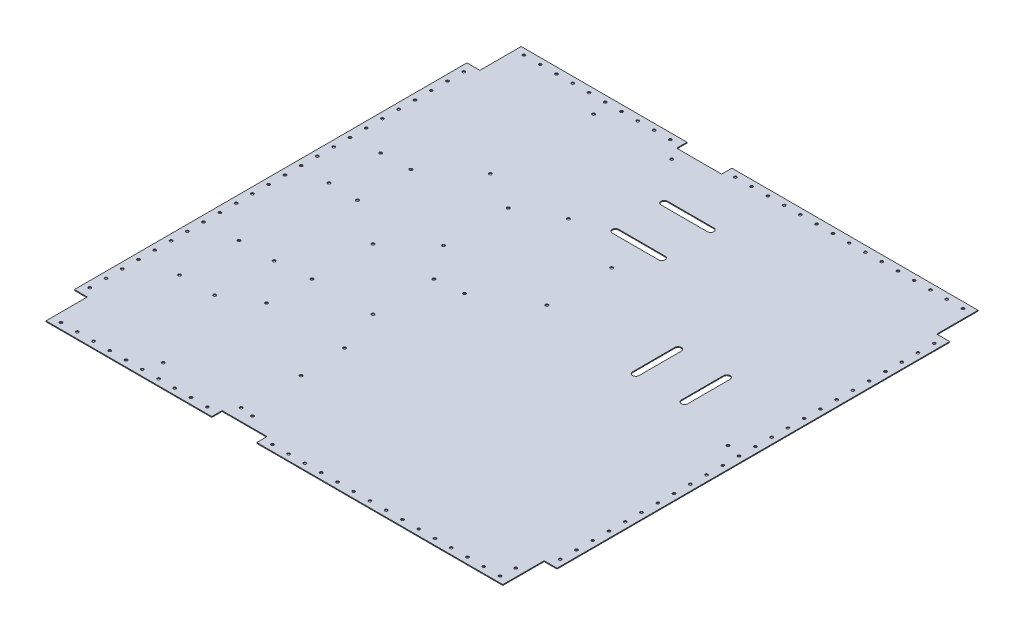
SolidWorks part; units mm, degrees
ref_plane "Front Plane" through (0, 0, 0) normal (0, 0, 1) x (1, 0, 0)
ref_plane "Top Plane" through (0, 0, 0) normal (0, 1, 0) x (1, 0, 0)
ref_plane "Right Plane" through (0, 0, 0) normal (1, 0, 0) x (0, 0, -1)
sketch "Sketch1" plane through (0, 0, 0) normal (0, 1, 0) x (1, 0, 0)
  line L1 (0, 0) -> (914.4, 0)
  line L2 (0, 0) -> (0, 609.6)
  line L3 (0, 609.6) -> (914.4, 609.6)
  line L4 (914.4, 0) -> (914.4, 609.6)
  dimension "D1" = 914.4
  dimension "D2" = 609.6
base flange "Base-Flange1" sketch "Sketch1" thickness 1.016 reverse thickness direction no parameters "D1"=0.7366
sketch "Sketch6" plane through (0, 0, 0) normal (0, 1, 0) x (1, 0, 0)
  line L0 (0, 0) -> (914.4, 0) construction
  line L1 (176.255, 597.025) -> (380.175, 597.025)
  line L2 (160.375, 546.225) -> (160.375, 63.375)
  line L3 (176.255, 12.575) -> (380.175, 12.575)
  line L4 (754.025, 546.225) -> (754.025, 63.375)
  line L5 (176.255, 581.3911) -> (738.145, 28.2089) construction
  line L6 (176.255, 28.2089) -> (738.145, 581.3911) construction
  line L7 (914.4, 0) -> (914.4, 609.6) construction
  line L8 (160.375, 304.8) -> (754.025, 304.8) construction
  line L10 (380.175, 597.025) -> (380.175, 584.325)
  line L11 (380.175, 584.325) -> (435.475, 584.325)
  line L12 (435.475, 597.025) -> (435.475, 584.325)
  line L15 (754.025, 546.225) -> (738.145, 546.225)
  line L16 (738.145, 597.025) -> (738.145, 546.225)
  line L17 (435.475, 12.575) -> (435.475, 25.275)
  line L18 (380.175, 12.575) -> (380.175, 25.275)
  line L19 (380.175, 25.275) -> (435.475, 25.275)
  line L20 (754.025, 63.375) -> (738.145, 63.375)
  line L21 (738.145, 12.575) -> (738.145, 63.375)
  line L22 (457.2, 597.025) -> (457.2, 12.575) construction
  line L23 (176.255, 12.575) -> (176.255, 63.375)
  line L24 (160.375, 63.375) -> (176.255, 63.375)
  line L25 (160.375, 546.225) -> (176.255, 546.225)
  line L26 (176.255, 597.025) -> (176.255, 546.225)
  line L27 (0, 609.6) -> (0, 0) construction
  line L28 (435.475, 597.025) -> (738.145, 597.025)
  line L29 (435.475, 12.575) -> (738.145, 12.575)
  point P0 (457.2, 304.8)
  dimension "D1" = 304.8
  dimension "D2" = 457.2
  dimension "D3" = 160.375
  dimension "D4" = 12.575
  dimension "D5" = 219.8
  dimension "D6" = 55.3
  dimension "D7" = 50.8
  dimension "D8" = 15.88
  dimension "D9" = 12.7
  dimension "D10" = 28.2089
extrude "Cut-Extrude1" cut sketch "Sketch6" against normal blind 10 flip side to cut normal cut yes
sketch "Sketch8" plane through (0, -1.016, 0) normal (0, -1, 0) x (1, 0, 0)
  line L0 (754.025, -546.225) -> (754.025, -63.375) construction
  line L1 (754.025, -63.375) -> (738.145, -63.375) construction
  line L20 (176.255, -597.025) -> (380.175, -597.025)
  line L21 (380.175, -597.025) -> (380.175, -584.325)
  line L22 (380.175, -584.325) -> (435.475, -584.325)
  line L23 (435.475, -584.325) -> (435.475, -597.025)
  line L24 (435.475, -597.025) -> (738.145, -597.025)
  line L25 (738.145, -597.025) -> (738.145, -546.225)
  line L26 (738.145, -546.225) -> (754.025, -546.225)
  line L27 (754.025, -546.225) -> (754.025, -63.375)
  line L28 (754.025, -63.375) -> (738.145, -63.375)
  line L29 (738.145, -63.375) -> (738.145, -12.575)
  line L30 (738.145, -12.575) -> (435.475, -12.575)
  line L31 (435.475, -12.575) -> (435.475, -25.275)
  line L32 (435.475, -25.275) -> (380.175, -25.275)
  line L33 (380.175, -25.275) -> (380.175, -12.575)
  line L34 (380.175, -12.575) -> (176.255, -12.575)
  line L35 (176.255, -12.575) -> (176.255, -63.375)
  line L36 (176.255, -63.375) -> (160.375, -63.375)
  line L37 (160.375, -63.375) -> (160.375, -546.225)
  line L38 (160.375, -546.225) -> (176.255, -546.225)
  line L39 (176.255, -546.225) -> (176.255, -597.025)
  line L40 (176.255, -597.025) -> (380.175, -597.025)
  line L41 (380.175, -597.025) -> (380.175, -584.325)
  line L42 (380.175, -584.325) -> (435.475, -584.325)
  line L43 (435.475, -584.325) -> (435.475, -597.025)
  line L44 (435.475, -597.025) -> (738.145, -597.025)
  line L45 (738.145, -597.025) -> (738.145, -546.225)
  line L46 (738.145, -546.225) -> (754.025, -546.225)
  line L47 (754.025, -546.225) -> (754.025, -63.375)
  line L48 (754.025, -63.375) -> (738.145, -63.375)
  line L49 (738.145, -63.375) -> (738.145, -12.575)
  line L50 (738.145, -12.575) -> (435.475, -12.575)
  line L51 (435.475, -12.575) -> (435.475, -25.275)
  line L52 (435.475, -25.275) -> (380.175, -25.275)
  line L53 (380.175, -25.275) -> (380.175, -12.575)
  line L54 (380.175, -12.575) -> (176.255, -12.575)
  line L55 (176.255, -12.575) -> (176.255, -63.375)
  line L56 (176.255, -63.375) -> (160.375, -63.375)
  line L57 (160.375, -63.375) -> (160.375, -546.225)
  line L58 (160.375, -546.225) -> (176.255, -546.225)
  line L59 (176.255, -546.225) -> (176.255, -597.025)
  circle A0 centre (167.875, -534.8) radius 1.675
  circle A1 centre (167.875, -514.8) radius 1.675
  circle A2 centre (167.875, -494.8) radius 1.675
  circle A3 centre (167.875, -474.8) radius 1.675
  circle A4 centre (167.875, -454.8) radius 1.675
  circle A5 centre (167.875, -434.8) radius 1.675
  circle A6 centre (167.875, -414.8) radius 1.675
  circle A7 centre (167.875, -394.8) radius 1.675
  circle A8 centre (167.875, -374.8) radius 1.675
  circle A9 centre (167.875, -354.8) radius 1.675
  circle A10 centre (167.875, -334.8) radius 1.675
  circle A11 centre (167.875, -314.8) radius 1.675
  circle A12 centre (167.875, -294.8) radius 1.675
  circle A13 centre (167.875, -274.8) radius 1.675
  circle A14 centre (167.875, -254.8) radius 1.675
  circle A15 centre (167.875, -234.8) radius 1.675
  circle A16 centre (167.875, -214.8) radius 1.675
  circle A17 centre (167.875, -194.8) radius 1.675
  circle A18 centre (167.875, -174.8) radius 1.675
  circle A19 centre (167.875, -154.8) radius 1.675
  circle A20 centre (167.875, -134.8) radius 1.675
  circle A21 centre (167.875, -114.8) radius 1.675
  circle A22 centre (167.875, -94.8) radius 1.675
  circle A23 centre (167.875, -74.8) radius 1.675
  circle A24 centre (187.2, -20.075) radius 1.675
  circle A25 centre (207.2, -20.075) radius 1.675
  circle A26 centre (227.2, -20.075) radius 1.675
  circle A27 centre (247.2, -20.075) radius 1.675
  circle A28 centre (267.2, -20.075) radius 1.675
  circle A29 centre (287.2, -20.075) radius 1.675
  circle A30 centre (307.2, -20.075) radius 1.675
  circle A31 centre (327.2, -20.075) radius 1.675
  circle A32 centre (347.2, -20.075) radius 1.675
  circle A33 centre (367.2, -20.075) radius 1.675
  circle A34 centre (447.2, -20.075) radius 1.675
  circle A35 centre (467.2, -20.075) radius 1.675
  circle A36 centre (487.2, -20.075) radius 1.675
  circle A37 centre (507.2, -20.075) radius 1.675
  circle A38 centre (527.2, -20.075) radius 1.675
  circle A39 centre (547.2, -20.075) radius 1.675
  circle A40 centre (567.2, -20.075) radius 1.675
  circle A41 centre (587.2, -20.075) radius 1.675
  circle A42 centre (607.2, -20.075) radius 1.675
  circle A43 centre (627.2, -20.075) radius 1.675
  circle A44 centre (647.2, -20.075) radius 1.675
  circle A45 centre (667.2, -20.075) radius 1.675
  circle A46 centre (687.2, -20.075) radius 1.675
  circle A47 centre (707.2, -20.075) radius 1.675
  circle A48 centre (727.2, -20.075) radius 1.675
  circle A49 centre (746.525, -74.8) radius 1.675
  circle A50 centre (746.525, -94.8) radius 1.675
  circle A51 centre (746.525, -114.8) radius 1.675
  circle A52 centre (746.525, -134.8) radius 1.675
  circle A53 centre (746.525, -154.8) radius 1.675
  circle A54 centre (746.525, -174.8) radius 1.675
  circle A55 centre (746.525, -194.8) radius 1.675
  circle A56 centre (746.525, -214.8) radius 1.675
  circle A57 centre (746.525, -234.8) radius 1.675
  circle A58 centre (746.525, -254.8) radius 1.675
  circle A59 centre (746.525, -274.8) radius 1.675
  circle A60 centre (746.525, -294.8) radius 1.675
  circle A61 centre (746.525, -314.8) radius 1.675
  circle A62 centre (746.525, -334.8) radius 1.675
  circle A63 centre (746.525, -354.8) radius 1.675
  circle A64 centre (746.525, -374.8) radius 1.675
  circle A65 centre (746.525, -394.8) radius 1.675
  circle A66 centre (746.525, -414.8) radius 1.675
  circle A67 centre (746.525, -434.8) radius 1.675
  circle A68 centre (746.525, -454.8) radius 1.675
  circle A69 centre (746.525, -474.8) radius 1.675
  circle A70 centre (746.525, -494.8) radius 1.675
  circle A71 centre (746.525, -514.8) radius 1.675
  circle A72 centre (746.525, -534.8) radius 1.675
  circle A73 centre (727.2, -589.525) radius 1.675
  circle A74 centre (707.2, -589.525) radius 1.675
  circle A75 centre (687.2, -589.525) radius 1.675
  circle A76 centre (667.2, -589.525) radius 1.675
  circle A77 centre (647.2, -589.525) radius 1.675
  circle A78 centre (627.2, -589.525) radius 1.675
  circle A79 centre (607.2, -589.525) radius 1.675
  circle A80 centre (587.2, -589.525) radius 1.675
  circle A81 centre (567.2, -589.525) radius 1.675
  circle A82 centre (547.2, -589.525) radius 1.675
  circle A83 centre (527.2, -589.525) radius 1.675
  circle A84 centre (507.2, -589.525) radius 1.675
  circle A85 centre (487.2, -589.525) radius 1.675
  circle A86 centre (467.2, -589.525) radius 1.675
  circle A87 centre (447.2, -589.525) radius 1.675
  circle A88 centre (367.2, -589.525) radius 1.675
  circle A89 centre (347.2, -589.525) radius 1.675
  circle A90 centre (327.2, -589.525) radius 1.675
  circle A91 centre (307.2, -589.525) radius 1.675
  circle A92 centre (287.2, -589.525) radius 1.675
  circle A93 centre (267.2, -589.525) radius 1.675
  circle A94 centre (247.2, -589.525) radius 1.675
  circle A95 centre (227.2, -589.525) radius 1.675
  circle A96 centre (207.2, -589.525) radius 1.675
  circle A97 centre (187.2, -589.525) radius 1.6325
  dimension "D2" = 3.35
  dimension "D3" = 3.265
  dimension "D1" = 0
extrude "Cut-Extrude2" cut sketch "Sketch8" against normal through all contours A30 | A29 | A28 | A27 | A26 | A24 | A25 | A31 | A32 | A33 | A34 | A35 | A36 | A37 | A38 | A39 | A40 | A41 | A42 | A44 | A43 | A45 | A46 | A47 | A48 | A49 | A50 | A51 | A52 | A53 | A54 | A55 | A56 | A57 | A58 | A59 | A60 | A61 | A62 | A63 | A64 | A65 | A66 | A67 | A68 | A69 | A70 | A71 | A72 | A73 | A74 | A75 | A76 | A77 | A78 | A79 | A80 | A81 | A82 | A83 | A84 | A85 | A86 | A87 | A88 | A89 | A90 | A91 | A92 | A93 | A94 | A97 | A96 | A95 | A0 | A1 | A2 | A3 | A4 | A5 | A6 | A7 | A8 | A9 | A10 | A11 | A12 | A13 | A14 | A15 | A16 | A17 | A18 | A19 | A20 | A21 | A22 | A23 normal cut yes
sketch "Sketch11" plane through (0, 0, 0) normal (0, 1, 0) x (1, 0, 0)
  line L0 (595.275, 371.025) -> (595.275, 319.025) construction
  line L1 (599.275, 371.025) -> (599.275, 319.025)
  line L2 (591.275, 371.025) -> (591.275, 319.025)
  line L3 (738.145, 597.025) -> (435.475, 597.025) construction
  line L4 (655.275, 371.025) -> (655.275, 319.025) construction
  line L5 (659.275, 371.025) -> (659.275, 319.025)
  line L6 (651.275, 371.025) -> (651.275, 319.025)
  line L7 (488.025, 458.275) -> (431.025, 458.275) construction
  line L8 (488.025, 454.275) -> (431.025, 454.275)
  line L9 (488.025, 462.275) -> (431.025, 462.275)
  line L10 (488.025, 518.275) -> (431.025, 518.275) construction
  line L11 (488.025, 514.275) -> (431.025, 514.275)
  line L12 (488.025, 522.275) -> (431.025, 522.275)
  line L13 (754.025, 63.375) -> (754.025, 546.225) construction
  arc A0 (599.275, 371.025) -> (591.275, 371.025) centre (595.275, 371.025) ccw
  arc A1 (591.275, 319.025) -> (599.275, 319.025) centre (595.275, 319.025) ccw
  arc A2 (659.275, 371.025) -> (651.275, 371.025) centre (655.275, 371.025) ccw
  arc A3 (651.275, 319.025) -> (659.275, 319.025) centre (655.275, 319.025) ccw
  arc A4 (488.025, 454.275) -> (488.025, 462.275) centre (488.025, 458.275) ccw
  arc A5 (431.025, 462.275) -> (431.025, 454.275) centre (431.025, 458.275) ccw
  arc A6 (488.025, 514.275) -> (488.025, 522.275) centre (488.025, 518.275) ccw
  arc A7 (431.025, 522.275) -> (431.025, 514.275) centre (431.025, 518.275) ccw
  point P2 (595.275, 345.025)
  point P7 (655.275, 345.025)
  point P18 (459.525, 458.275)
  point P23 (459.525, 518.275)
  dimension "D3" = 4
  dimension "D4" = 4
  dimension "D9" = 4
  dimension "D10" = 4
  dimension "D16" = 226
  dimension "D2" = 226
  dimension "D5" = 52
  dimension "D6" = 60
  dimension "D8" = 57
  dimension "D11" = 266
  dimension "D12" = 266
  dimension "D13" = 60
  dimension "D14" = 78.75
  dimension "D15" = 98.75
extrude "Cut-Extrude3" cut sketch "Sketch11" against normal through all normal cut yes
sketch "Sketch14" plane through (0, 0, 0) normal (0, 1, 0) x (1, 0, 0)
  circle A0 centre (203.375, 333.575) radius 1.75
  circle A1 centre (203.375, 397.175) radius 1.75
  circle A2 centre (239.375, 332.575) radius 1.75
  circle A3 centre (239.375, 398.175) radius 1.75
  circle A4 centre (295.375, 220.575) radius 1.75
  circle A5 centre (295.375, 295.575) radius 1.75
  circle A6 centre (370.375, 220.575) radius 1.75
  circle A7 centre (370.375, 295.575) radius 1.75
  circle A8 centre (292.875, 442.525) radius 1.75
  circle A9 centre (292.875, 569.525) radius 1.75
  circle A10 centre (388.875, 569.525) radius 1.75
  circle A11 centre (388.875, 442.525) radius 1.75
  circle A12 centre (252.6783, 143.5804) radius 1.75
  circle A13 centre (252.6783, 216.7804) radius 1.75
  circle A14 centre (209.4783, 216.7804) radius 1.75
  circle A15 centre (209.4783, 143.5804) radius 1.75
  circle A16 centre (292.875, 167.075) radius 1.75
  circle A17 centre (292.875, 40.075) radius 1.75
  circle A18 centre (388.875, 40.075) radius 1.75
  circle A19 centre (391.5449, 111.0551) radius 1.75
  circle A20 centre (388.875, 167.075) radius 1.75
  circle A21 centre (404.525, 299.075) radius 1.75
  circle A22 centre (404.525, 38.075) radius 1.75
  circle A23 centre (728.525, 38.075) radius 1.75
  circle A24 centre (728.525, 299.075) radius 1.75
  circle A25 centre (340.375, 417.025) radius 1.75
  circle A26 centre (340.375, 337.35) radius 1.75
  circle A27 centre (467.675, 337.35) radius 1.75
  circle A28 centre (467.675, 417.025) radius 1.75
  dimension "D1" = 3.5
extrude "Cut-Extrude4" cut sketch "Sketch14" against normal through all normal cut yes
sketch "Bend-Lines1" [suppressed] plane through (0, 0, 0) normal (0, 1, 0) x (1, 0, 0)
sketch "Bounding-Box1" [suppressed] plane through (0, 0, 0) normal (0, 1, 0) x (1, 0, 0)
sheet metal parameters "Sheet-Metal1" thickness 1.016 parameters "D1"=0.7366
flat pattern "Flat-Pattern1" [suppressed]
sketch "Bend-Lines2" plane through (0, 0, 0) normal (0, 1, 0) x (1, 0, 0)
sketch3d "Bounding-Box2" [suppressed]
  line L0 (914.4, 609.6, 0) -> (0, 609.6, 0) construction
  line L1 (914.4, 0, 0) -> (0, 0, 0) construction
  line L2 (914.4, 609.6, 0) -> (914.4, 0, 0) construction
  line L3 (0, 609.6, 0) -> (0, 0, 0) construction
sheet metal parameters "Sheet-Metal3" thickness 1.016 parameters "D1"=0.7366
flat pattern "Flat-Pattern1"
sketch "Bend-Lines2" plane through (0, 0, 0) normal (0, 1, 0) x (1, 0, 0)
sketch3d "Bounding-Box2" [suppressed]
  line L0 (754.025, 597.025, 0) -> (160.375, 597.025, 0) construction
  line L1 (754.025, 12.575, 0) -> (160.375, 12.575, 0) construction
  line L2 (754.025, 597.025, 0) -> (754.025, 12.575, 0) construction
  line L3 (160.375, 597.025, 0) -> (160.375, 12.575, 0) construction
sheet metal parameters "Sheet-Metal4" thickness 1.016 parameters "D1"=0.7366
flat pattern "Flat-Pattern1"
sketch "Bend-Lines2" plane through (0, 0, 0) normal (0, 1, 0) x (1, 0, 0)
sketch3d "Bounding-Box2" [suppressed]
  line L0 (754.025, 597.025, 0) -> (160.375, 597.025, 0) construction
  line L1 (754.025, 12.575, 0) -> (160.375, 12.575, 0) construction
  line L2 (754.025, 597.025, 0) -> (754.025, 12.575, 0) construction
  line L3 (160.375, 597.025, 0) -> (160.375, 12.575, 0) construction
sheet metal parameters "Sheet-Metal5" thickness 1.016 parameters "D1"=0.7366
flat pattern "Flat-Pattern5"
sketch "Bend-Lines4" plane through (0, 0, 0) normal (0, 1, 0) x (1, 0, 0)
sketch "Bounding-Box4" [suppressed] plane through (0, 0, 0) normal (0, 1, 0) x (1, 0, 0)
sheet metal parameters "Sheet-Metal6" thickness 1.016 parameters "D1"=0.7366
flat pattern "Flat-Pattern6"
sketch "Bend-Lines5" plane through (0, 0, 0) normal (0, 1, 0) x (1, 0, 0)
sketch "Bounding-Box5" [suppressed] plane through (0, 0, 0) normal (0, 1, 0) x (1, 0, 0)
sheet metal parameters "Sheet-Metal7" thickness 1.016 parameters "D1"=0.7366
flat pattern "Flat-Pattern1"
sketch "Bend-Lines2" plane through (0, 0, 0) normal (0, 1, 0) x (1, 0, 0)
sketch3d "Bounding-Box2" [suppressed]
  line L0 (754.025, 597.025, 0) -> (160.375, 597.025, 0) construction
  line L1 (754.025, 12.575, 0) -> (160.375, 12.575, 0) construction
  line L2 (754.025, 597.025, 0) -> (754.025, 12.575, 0) construction
  line L3 (160.375, 597.025, 0) -> (160.375, 12.575, 0) construction
sheet metal parameters "Sheet-Metal8" thickness 1.016 parameters "D1"=0.7366
flat pattern "Flat-Pattern8"
sketch "Bend-Lines7" plane through (0, 0, 0) normal (0, 1, 0) x (1, 0, 0)
sketch "Bounding-Box7" [suppressed] plane through (0, 0, 0) normal (0, 1, 0) x (1, 0, 0)
sheet metal parameters "Sheet-Metal9" thickness 1.016 parameters "D1"=0.7366
flat pattern "Flat-Pattern9"
sketch "Bend-Lines8" plane through (0, 0, 0) normal (0, 1, 0) x (1, 0, 0)
sketch "Bounding-Box8" [suppressed] plane through (0, 0, 0) normal (0, 1, 0) x (1, 0, 0)
sheet metal parameters "Sheet-Metal10" thickness 1.016 parameters "D1"=0.7366
flat pattern "Flat-Pattern10"
sketch "Bend-Lines9" plane through (0, 0, 0) normal (0, 1, 0) x (1, 0, 0)
sketch "Bounding-Box9" [suppressed] plane through (0, 0, 0) normal (0, 1, 0) x (1, 0, 0)
sheet metal parameters "Sheet-Metal11" thickness 1.016 parameters "D1"=0.7366
flat pattern "Flat-Pattern11"
sketch "Bend-Lines10" plane through (0, 0, 0) normal (0, 1, 0) x (1, 0, 0)
sketch "Bounding-Box10" [suppressed] plane through (0, 0, 0) normal (0, 1, 0) x (1, 0, 0)
sheet metal parameters "Sheet-Metal12" thickness 1.016 parameters "D1"=0.7366
flat pattern "Flat-Pattern12"
sketch "Bend-Lines11" plane through (0, 0, 0) normal (0, 1, 0) x (1, 0, 0)
sketch "Bounding-Box11" [suppressed] plane through (0, 0, 0) normal (0, 1, 0) x (1, 0, 0)
sheet metal parameters "Sheet-Metal13" thickness 1.016 parameters "D1"=0.7366
flat pattern "Flat-Pattern13"
sketch "Bend-Lines12" plane through (0, 0, 0) normal (0, 1, 0) x (1, 0, 0)
sketch "Bounding-Box12" [suppressed] plane through (0, 0, 0) normal (0, 1, 0) x (1, 0, 0)
sheet metal parameters "Sheet-Metal14" thickness 1.016 parameters "D1"=0.7366
flat pattern "Flat-Pattern14"
sketch "Bend-Lines13" plane through (0, 0, 0) normal (0, 1, 0) x (1, 0, 0)
sketch "Bounding-Box13" [suppressed] plane through (0, 0, 0) normal (0, 1, 0) x (1, 0, 0)
sheet metal parameters "Sheet-Metal15" thickness 1.016 parameters "D1"=0.7366
flat pattern "Flat-Pattern15"
sketch "Bend-Lines14" plane through (0, 0, 0) normal (0, 1, 0) x (1, 0, 0)
sketch "Bounding-Box14" [suppressed] plane through (0, 0, 0) normal (0, 1, 0) x (1, 0, 0)
sheet metal parameters "Sheet-Metal16" thickness 1.016 parameters "D1"=0.7366
flat pattern "Flat-Pattern16"
sketch "Bend-Lines15" plane through (0, 0, 0) normal (0, 1, 0) x (1, 0, 0)
sketch "Bounding-Box15" [suppressed] plane through (0, 0, 0) normal (0, 1, 0) x (1, 0, 0)
sheet metal parameters "Sheet-Metal17" thickness 1.016 parameters "D1"=0.7366
flat pattern "Flat-Pattern17"
sketch "Bend-Lines16" plane through (0, 0, 0) normal (0, 1, 0) x (1, 0, 0)
sketch "Bounding-Box16" [suppressed] plane through (0, 0, 0) normal (0, 1, 0) x (1, 0, 0)
sheet metal parameters "Sheet-Metal18" thickness 1.016 parameters "D1"=0.7366
flat pattern "Flat-Pattern18"
sketch "Bend-Lines17" plane through (0, 0, 0) normal (0, 1, 0) x (1, 0, 0)
sketch "Bounding-Box17" [suppressed] plane through (0, 0, 0) normal (0, 1, 0) x (1, 0, 0)
sheet metal parameters "Sheet-Metal19" thickness 1.016 parameters "D1"=0.7366
flat pattern "Flat-Pattern19"
sketch "Bend-Lines18" plane through (0, 0, 0) normal (0, 1, 0) x (1, 0, 0)
sketch "Bounding-Box18" [suppressed] plane through (0, 0, 0) normal (0, 1, 0) x (1, 0, 0)
sheet metal parameters "Sheet-Metal20" thickness 1.016 parameters "D1"=0.7366
flat pattern "Flat-Pattern20"
sketch "Bend-Lines19" plane through (0, 0, 0) normal (0, 1, 0) x (1, 0, 0)
sketch "Bounding-Box19" [suppressed] plane through (0, 0, 0) normal (0, 1, 0) x (1, 0, 0)
sheet metal parameters "Sheet-Metal21" thickness 1.016 parameters "D1"=0.7366
flat pattern "Flat-Pattern21"
sketch "Bend-Lines20" plane through (0, 0, 0) normal (0, 1, 0) x (1, 0, 0)
sketch "Bounding-Box20" [suppressed] plane through (0, 0, 0) normal (0, 1, 0) x (1, 0, 0)
sheet metal parameters "Sheet-Metal22" thickness 1.016 parameters "D1"=0.7366
flat pattern "Flat-Pattern22"
sketch "Bend-Lines21" plane through (0, 0, 0) normal (0, 1, 0) x (1, 0, 0)
sketch "Bounding-Box21" [suppressed] plane through (0, 0, 0) normal (0, 1, 0) x (1, 0, 0)
sheet metal parameters "Sheet-Metal23" thickness 1.016 parameters "D1"=0.7366
flat pattern "Flat-Pattern23"
sketch "Bend-Lines22" plane through (0, 0, 0) normal (0, 1, 0) x (1, 0, 0)
sketch "Bounding-Box22" [suppressed] plane through (0, 0, 0) normal (0, 1, 0) x (1, 0, 0)
sheet metal parameters "Sheet-Metal24" thickness 1.016 parameters "D1"=0.7366
flat pattern "Flat-Pattern24"
sketch "Bend-Lines23" plane through (0, 0, 0) normal (0, 1, 0) x (1, 0, 0)
sketch "Bounding-Box23" [suppressed] plane through (0, 0, 0) normal (0, 1, 0) x (1, 0, 0)
sheet metal parameters "Sheet-Metal25" thickness 1.016 parameters "D1"=0.7366
flat pattern "Flat-Pattern25"
sketch "Bend-Lines24" plane through (0, 0, 0) normal (0, 1, 0) x (1, 0, 0)
sketch "Bounding-Box24" [suppressed] plane through (0, 0, 0) normal (0, 1, 0) x (1, 0, 0)
sheet metal parameters "Sheet-Metal26" thickness 1.016 parameters "D1"=0.7366
flat pattern "Flat-Pattern26"
sketch "Bend-Lines25" plane through (0, 0, 0) normal (0, 1, 0) x (1, 0, 0)
sketch "Bounding-Box25" [suppressed] plane through (0, 0, 0) normal (0, 1, 0) x (1, 0, 0)
sheet metal parameters "Sheet-Metal27" thickness 1.016 parameters "D1"=0.7366
flat pattern "Flat-Pattern27"
sketch "Bend-Lines26" plane through (0, 0, 0) normal (0, 1, 0) x (1, 0, 0)
sketch "Bounding-Box26" [suppressed] plane through (0, 0, 0) normal (0, 1, 0) x (1, 0, 0)
sheet metal parameters "Sheet-Metal28" thickness 1.016 parameters "D1"=0.7366
flat pattern "Flat-Pattern28"
sketch "Bend-Lines27" plane through (0, 0, 0) normal (0, 1, 0) x (1, 0, 0)
sketch "Bounding-Box27" [suppressed] plane through (0, 0, 0) normal (0, 1, 0) x (1, 0, 0)
sheet metal parameters "Sheet-Metal29" thickness 1.016 parameters "D1"=0.7366
flat pattern "Flat-Pattern29"
sketch "Bend-Lines28" plane through (0, 0, 0) normal (0, 1, 0) x (1, 0, 0)
sketch "Bounding-Box28" [suppressed] plane through (0, 0, 0) normal (0, 1, 0) x (1, 0, 0)
sheet metal parameters "Sheet-Metal30" thickness 1.016 parameters "D1"=0.7366
flat pattern "Flat-Pattern30"
sketch "Bend-Lines29" plane through (0, 0, 0) normal (0, 1, 0) x (1, 0, 0)
sketch "Bounding-Box29" [suppressed] plane through (0, 0, 0) normal (0, 1, 0) x (1, 0, 0)
sheet metal parameters "Sheet-Metal31" thickness 1.016 parameters "D1"=0.7366
flat pattern "Flat-Pattern31"
sketch "Bend-Lines30" plane through (0, 0, 0) normal (0, 1, 0) x (1, 0, 0)
sketch "Bounding-Box30" [suppressed] plane through (0, 0, 0) normal (0, 1, 0) x (1, 0, 0)
sheet metal parameters "Sheet-Metal32" thickness 1.016 parameters "D1"=0.7366
flat pattern "Flat-Pattern32"
sketch "Bend-Lines31" plane through (0, 0, 0) normal (0, 1, 0) x (1, 0, 0)
sketch "Bounding-Box31" [suppressed] plane through (0, 0, 0) normal (0, 1, 0) x (1, 0, 0)
sheet metal parameters "Sheet-Metal33" thickness 1.016 parameters "D1"=0.7366
flat pattern "Flat-Pattern33"
sketch "Bend-Lines32" plane through (0, 0, 0) normal (0, 1, 0) x (1, 0, 0)
sketch "Bounding-Box32" [suppressed] plane through (0, 0, 0) normal (0, 1, 0) x (1, 0, 0)
sheet metal parameters "Sheet-Metal34" thickness 1.016 parameters "D1"=0.7366
flat pattern "Flat-Pattern34"
sketch "Bend-Lines33" plane through (0, 0, 0) normal (0, 1, 0) x (1, 0, 0)
sketch "Bounding-Box33" [suppressed] plane through (0, 0, 0) normal (0, 1, 0) x (1, 0, 0)
sheet metal parameters "Sheet-Metal35" thickness 1.016 parameters "D1"=0.7366
flat pattern "Flat-Pattern35"
sketch "Bend-Lines34" plane through (0, 0, 0) normal (0, 1, 0) x (1, 0, 0)
sketch "Bounding-Box34" [suppressed] plane through (0, 0, 0) normal (0, 1, 0) x (1, 0, 0)
sheet metal parameters "Sheet-Metal36" thickness 1.016 parameters "D1"=0.7366
flat pattern "Flat-Pattern36"
sketch "Bend-Lines35" plane through (0, 0, 0) normal (0, 1, 0) x (1, 0, 0)
sketch "Bounding-Box35" [suppressed] plane through (0, 0, 0) normal (0, 1, 0) x (1, 0, 0)
sheet metal parameters "Sheet-Metal37" thickness 1.016 parameters "D1"=0.7366
flat pattern "Flat-Pattern37"
sketch "Bend-Lines36" plane through (0, 0, 0) normal (0, 1, 0) x (1, 0, 0)
sketch "Bounding-Box36" [suppressed] plane through (0, 0, 0) normal (0, 1, 0) x (1, 0, 0)
sheet metal parameters "Sheet-Metal38" thickness 1.016 parameters "D1"=0.7366
flat pattern "Flat-Pattern38"
sketch "Bend-Lines37" plane through (0, 0, 0) normal (0, 1, 0) x (1, 0, 0)
sketch "Bounding-Box37" [suppressed] plane through (0, 0, 0) normal (0, 1, 0) x (1, 0, 0)
sheet metal parameters "Sheet-Metal39" thickness 1.016 parameters "D1"=0.7366
flat pattern "Flat-Pattern39"
sketch "Bend-Lines38" plane through (0, 0, 0) normal (0, 1, 0) x (1, 0, 0)
sketch "Bounding-Box38" [suppressed] plane through (0, 0, 0) normal (0, 1, 0) x (1, 0, 0)
sheet metal parameters "Sheet-Metal40" thickness 1.016 parameters "D1"=0.7366
flat pattern "Flat-Pattern40"
sketch "Bend-Lines39" plane through (0, 0, 0) normal (0, 1, 0) x (1, 0, 0)
sketch "Bounding-Box39" [suppressed] plane through (0, 0, 0) normal (0, 1, 0) x (1, 0, 0)
sheet metal parameters "Sheet-Metal41" thickness 1.016 parameters "D1"=0.7366
flat pattern "Flat-Pattern41"
sketch "Bend-Lines40" plane through (0, 0, 0) normal (0, 1, 0) x (1, 0, 0)
sketch "Bounding-Box40" [suppressed] plane through (0, 0, 0) normal (0, 1, 0) x (1, 0, 0)
sheet metal parameters "Sheet-Metal42" thickness 1.016 parameters "D1"=0.7366
flat pattern "Flat-Pattern42"
sketch "Bend-Lines41" plane through (0, 0, 0) normal (0, 1, 0) x (1, 0, 0)
sketch "Bounding-Box41" [suppressed] plane through (0, 0, 0) normal (0, 1, 0) x (1, 0, 0)
sheet metal parameters "Sheet-Metal43" thickness 1.016 parameters "D1"=0.7366
flat pattern "Flat-Pattern43"
sketch "Bend-Lines42" plane through (0, 0, 0) normal (0, 1, 0) x (1, 0, 0)
sketch "Bounding-Box42" [suppressed] plane through (0, 0, 0) normal (0, 1, 0) x (1, 0, 0)
sheet metal parameters "Sheet-Metal44" thickness 1.016 parameters "D1"=0.7366
flat pattern "Flat-Pattern44"
sketch "Bend-Lines43" plane through (0, 0, 0) normal (0, 1, 0) x (1, 0, 0)
sketch "Bounding-Box43" [suppressed] plane through (0, 0, 0) normal (0, 1, 0) x (1, 0, 0)
sheet metal parameters "Sheet-Metal45" thickness 1.016 parameters "D1"=0.7366
flat pattern "Flat-Pattern45"
sketch "Bend-Lines44" plane through (0, 0, 0) normal (0, 1, 0) x (1, 0, 0)
sketch "Bounding-Box44" [suppressed] plane through (0, 0, 0) normal (0, 1, 0) x (1, 0, 0)
sheet metal parameters "Sheet-Metal46" thickness 1.016 parameters "D1"=0.7366
flat pattern "Flat-Pattern46"
sketch "Bend-Lines45" plane through (0, 0, 0) normal (0, 1, 0) x (1, 0, 0)
sketch "Bounding-Box45" [suppressed] plane through (0, 0, 0) normal (0, 1, 0) x (1, 0, 0)
sheet metal parameters "Sheet-Metal47" thickness 1.016 parameters "D1"=0.7366
flat pattern "Flat-Pattern47"
sketch "Bend-Lines46" plane through (0, 0, 0) normal (0, 1, 0) x (1, 0, 0)
sketch "Bounding-Box46" [suppressed] plane through (0, 0, 0) normal (0, 1, 0) x (1, 0, 0)
sheet metal parameters "Sheet-Metal48" thickness 1.016 parameters "D1"=0.7366
flat pattern "Flat-Pattern48"
sketch "Bend-Lines47" plane through (0, 0, 0) normal (0, 1, 0) x (1, 0, 0)
sketch "Bounding-Box47" [suppressed] plane through (0, 0, 0) normal (0, 1, 0) x (1, 0, 0)
sheet metal parameters "Sheet-Metal49" thickness 1.016 parameters "D1"=0.7366
flat pattern "Flat-Pattern49"
sketch "Bend-Lines48" plane through (0, 0, 0) normal (0, 1, 0) x (1, 0, 0)
sketch "Bounding-Box48" [suppressed] plane through (0, 0, 0) normal (0, 1, 0) x (1, 0, 0)
sheet metal parameters "Sheet-Metal50" thickness 1.016 parameters "D1"=0.7366
flat pattern "Flat-Pattern50"
sketch "Bend-Lines49" plane through (0, 0, 0) normal (0, 1, 0) x (1, 0, 0)
sketch "Bounding-Box49" [suppressed] plane through (0, 0, 0) normal (0, 1, 0) x (1, 0, 0)
sheet metal parameters "Sheet-Metal51" thickness 1.016 parameters "D1"=0.7366
flat pattern "Flat-Pattern51"
sketch "Bend-Lines50" plane through (0, 0, 0) normal (0, 1, 0) x (1, 0, 0)
sketch "Bounding-Box50" [suppressed] plane through (0, 0, 0) normal (0, 1, 0) x (1, 0, 0)
sheet metal parameters "Sheet-Metal52" thickness 1.016 parameters "D1"=0.7366
flat pattern "Flat-Pattern52"
sketch "Bend-Lines51" plane through (0, 0, 0) normal (0, 1, 0) x (1, 0, 0)
sketch "Bounding-Box51" [suppressed] plane through (0, 0, 0) normal (0, 1, 0) x (1, 0, 0)
sheet metal parameters "Sheet-Metal53" thickness 1.016 parameters "D1"=0.7366
flat pattern "Flat-Pattern53"
sketch "Bend-Lines52" plane through (0, 0, 0) normal (0, 1, 0) x (1, 0, 0)
sketch "Bounding-Box52" [suppressed] plane through (0, 0, 0) normal (0, 1, 0) x (1, 0, 0)
sheet metal parameters "Sheet-Metal54" thickness 1.016 parameters "D1"=0.7366
flat pattern "Flat-Pattern54"
sketch "Bend-Lines53" plane through (0, 0, 0) normal (0, 1, 0) x (1, 0, 0)
sketch "Bounding-Box53" [suppressed] plane through (0, 0, 0) normal (0, 1, 0) x (1, 0, 0)
sheet metal parameters "Sheet-Metal55" thickness 1.016 parameters "D1"=0.7366
flat pattern "Flat-Pattern55"
sketch "Bend-Lines54" plane through (0, 0, 0) normal (0, 1, 0) x (1, 0, 0)
sketch "Bounding-Box54" [suppressed] plane through (0, 0, 0) normal (0, 1, 0) x (1, 0, 0)
sheet metal parameters "Sheet-Metal56" thickness 1.016 parameters "D1"=0.7366
flat pattern "Flat-Pattern56"
sketch "Bend-Lines55" plane through (0, 0, 0) normal (0, 1, 0) x (1, 0, 0)
sketch "Bounding-Box55" [suppressed] plane through (0, 0, 0) normal (0, 1, 0) x (1, 0, 0)
sheet metal parameters "Sheet-Metal57" thickness 1.016 parameters "D1"=0.7366
flat pattern "Flat-Pattern57"
sketch "Bend-Lines56" plane through (0, 0, 0) normal (0, 1, 0) x (1, 0, 0)
sketch "Bounding-Box56" [suppressed] plane through (0, 0, 0) normal (0, 1, 0) x (1, 0, 0)
sheet metal parameters "Sheet-Metal58" thickness 1.016 parameters "D1"=0.7366
flat pattern "Flat-Pattern58"
sketch "Bend-Lines57" plane through (0, 0, 0) normal (0, 1, 0) x (1, 0, 0)
sketch "Bounding-Box57" [suppressed] plane through (0, 0, 0) normal (0, 1, 0) x (1, 0, 0)
sheet metal parameters "Sheet-Metal59" thickness 1.016 parameters "D1"=0.7366
flat pattern "Flat-Pattern59"
sketch "Bend-Lines58" plane through (0, 0, 0) normal (0, 1, 0) x (1, 0, 0)
sketch "Bounding-Box58" [suppressed] plane through (0, 0, 0) normal (0, 1, 0) x (1, 0, 0)
sheet metal parameters "Sheet-Metal60" thickness 1.016 parameters "D1"=0.7366
flat pattern "Flat-Pattern60"
sketch "Bend-Lines59" plane through (0, 0, 0) normal (0, 1, 0) x (1, 0, 0)
sketch "Bounding-Box59" [suppressed] plane through (0, 0, 0) normal (0, 1, 0) x (1, 0, 0)
sheet metal parameters "Sheet-Metal61" thickness 1.016 parameters "D1"=0.7366
flat pattern "Flat-Pattern61"
sketch "Bend-Lines60" plane through (0, 0, 0) normal (0, 1, 0) x (1, 0, 0)
sketch "Bounding-Box60" [suppressed] plane through (0, 0, 0) normal (0, 1, 0) x (1, 0, 0)
sheet metal parameters "Sheet-Metal62" thickness 1.016 parameters "D1"=0.7366
flat pattern "Flat-Pattern62"
sketch "Bend-Lines61" plane through (0, 0, 0) normal (0, 1, 0) x (1, 0, 0)
sketch "Bounding-Box61" [suppressed] plane through (0, 0, 0) normal (0, 1, 0) x (1, 0, 0)
sheet metal parameters "Sheet-Metal63" thickness 1.016 parameters "D1"=0.7366
flat pattern "Flat-Pattern63"
sketch "Bend-Lines62" plane through (0, 0, 0) normal (0, 1, 0) x (1, 0, 0)
sketch "Bounding-Box62" [suppressed] plane through (0, 0, 0) normal (0, 1, 0) x (1, 0, 0)
sheet metal parameters "Sheet-Metal64" thickness 1.016 parameters "D1"=0.7366
flat pattern "Flat-Pattern64"
sketch "Bend-Lines63" plane through (0, 0, 0) normal (0, 1, 0) x (1, 0, 0)
sketch "Bounding-Box63" [suppressed] plane through (0, 0, 0) normal (0, 1, 0) x (1, 0, 0)
sheet metal parameters "Sheet-Metal65" thickness 1.016 parameters "D1"=0.7366
flat pattern "Flat-Pattern65"
sketch "Bend-Lines64" plane through (0, 0, 0) normal (0, 1, 0) x (1, 0, 0)
sketch "Bounding-Box64" [suppressed] plane through (0, 0, 0) normal (0, 1, 0) x (1, 0, 0)
sheet metal parameters "Sheet-Metal66" thickness 1.016 parameters "D1"=0.7366
flat pattern "Flat-Pattern66"
sketch "Bend-Lines65" plane through (0, 0, 0) normal (0, 1, 0) x (1, 0, 0)
sketch "Bounding-Box65" [suppressed] plane through (0, 0, 0) normal (0, 1, 0) x (1, 0, 0)
sheet metal parameters "Sheet-Metal67" thickness 1.016 parameters "D1"=0.7366
flat pattern "Flat-Pattern67"
sketch "Bend-Lines66" plane through (0, 0, 0) normal (0, 1, 0) x (1, 0, 0)
sketch "Bounding-Box66" [suppressed] plane through (0, 0, 0) normal (0, 1, 0) x (1, 0, 0)
sheet metal parameters "Sheet-Metal68" thickness 1.016 parameters "D1"=0.7366
flat pattern "Flat-Pattern68"
sketch "Bend-Lines67" plane through (0, 0, 0) normal (0, 1, 0) x (1, 0, 0)
sketch "Bounding-Box67" [suppressed] plane through (0, 0, 0) normal (0, 1, 0) x (1, 0, 0)
sheet metal parameters "Sheet-Metal69" thickness 1.016 parameters "D1"=0.7366
flat pattern "Flat-Pattern69"
sketch "Bend-Lines68" plane through (0, 0, 0) normal (0, 1, 0) x (1, 0, 0)
sketch "Bounding-Box68" [suppressed] plane through (0, 0, 0) normal (0, 1, 0) x (1, 0, 0)
sheet metal parameters "Sheet-Metal70" thickness 1.016 parameters "D1"=0.7366
flat pattern "Flat-Pattern70"
sketch "Bend-Lines69" plane through (0, 0, 0) normal (0, 1, 0) x (1, 0, 0)
sketch "Bounding-Box69" [suppressed] plane through (0, 0, 0) normal (0, 1, 0) x (1, 0, 0)
sheet metal parameters "Sheet-Metal71" thickness 1.016 parameters "D1"=0.7366
flat pattern "Flat-Pattern71"
sketch "Bend-Lines70" plane through (0, 0, 0) normal (0, 1, 0) x (1, 0, 0)
sketch "Bounding-Box70" [suppressed] plane through (0, 0, 0) normal (0, 1, 0) x (1, 0, 0)
sheet metal parameters "Sheet-Metal72" thickness 1.016 parameters "D1"=0.7366
flat pattern "Flat-Pattern72"
sketch "Bend-Lines71" plane through (0, 0, 0) normal (0, 1, 0) x (1, 0, 0)
sketch "Bounding-Box71" [suppressed] plane through (0, 0, 0) normal (0, 1, 0) x (1, 0, 0)
sheet metal parameters "Sheet-Metal73" thickness 1.016 parameters "D1"=0.7366
flat pattern "Flat-Pattern73"
sketch "Bend-Lines72" plane through (0, 0, 0) normal (0, 1, 0) x (1, 0, 0)
sketch "Bounding-Box72" [suppressed] plane through (0, 0, 0) normal (0, 1, 0) x (1, 0, 0)
sheet metal parameters "Sheet-Metal74" thickness 1.016 parameters "D1"=0.7366
flat pattern "Flat-Pattern74"
sketch "Bend-Lines73" plane through (0, 0, 0) normal (0, 1, 0) x (1, 0, 0)
sketch "Bounding-Box73" [suppressed] plane through (0, 0, 0) normal (0, 1, 0) x (1, 0, 0)
sheet metal parameters "Sheet-Metal75" thickness 1.016 parameters "D1"=0.7366
flat pattern "Flat-Pattern75"
sketch "Bend-Lines74" plane through (0, 0, 0) normal (0, 1, 0) x (1, 0, 0)
sketch "Bounding-Box74" [suppressed] plane through (0, 0, 0) normal (0, 1, 0) x (1, 0, 0)
sheet metal parameters "Sheet-Metal76" thickness 1.016 parameters "D1"=0.7366
flat pattern "Flat-Pattern76"
sketch "Bend-Lines75" plane through (0, 0, 0) normal (0, 1, 0) x (1, 0, 0)
sketch "Bounding-Box75" [suppressed] plane through (0, 0, 0) normal (0, 1, 0) x (1, 0, 0)
sheet metal parameters "Sheet-Metal77" thickness 1.016 parameters "D1"=0.7366
flat pattern "Flat-Pattern77"
sketch "Bend-Lines76" plane through (0, 0, 0) normal (0, 1, 0) x (1, 0, 0)
sketch "Bounding-Box76" [suppressed] plane through (0, 0, 0) normal (0, 1, 0) x (1, 0, 0)
sheet metal parameters "Sheet-Metal78" thickness 1.016 parameters "D1"=0.7366
flat pattern "Flat-Pattern78"
sketch "Bend-Lines77" plane through (0, 0, 0) normal (0, 1, 0) x (1, 0, 0)
sketch "Bounding-Box77" [suppressed] plane through (0, 0, 0) normal (0, 1, 0) x (1, 0, 0)
sheet metal parameters "Sheet-Metal79" thickness 1.016 parameters "D1"=0.7366
flat pattern "Flat-Pattern79"
sketch "Bend-Lines78" plane through (0, 0, 0) normal (0, 1, 0) x (1, 0, 0)
sketch "Bounding-Box78" [suppressed] plane through (0, 0, 0) normal (0, 1, 0) x (1, 0, 0)
sheet metal parameters "Sheet-Metal80" thickness 1.016 parameters "D1"=0.7366
flat pattern "Flat-Pattern80"
sketch "Bend-Lines79" plane through (0, 0, 0) normal (0, 1, 0) x (1, 0, 0)
sketch "Bounding-Box79" [suppressed] plane through (0, 0, 0) normal (0, 1, 0) x (1, 0, 0)
sheet metal parameters "Sheet-Metal81" thickness 1.016 parameters "D1"=0.7366
flat pattern "Flat-Pattern81"
sketch "Bend-Lines80" plane through (0, 0, 0) normal (0, 1, 0) x (1, 0, 0)
sketch "Bounding-Box80" [suppressed] plane through (0, 0, 0) normal (0, 1, 0) x (1, 0, 0)
sheet metal parameters "Sheet-Metal82" thickness 1.016 parameters "D1"=0.7366
flat pattern "Flat-Pattern82"
sketch "Bend-Lines81" plane through (0, 0, 0) normal (0, 1, 0) x (1, 0, 0)
sketch "Bounding-Box81" [suppressed] plane through (0, 0, 0) normal (0, 1, 0) x (1, 0, 0)
sheet metal parameters "Sheet-Metal83" thickness 1.016 parameters "D1"=0.7366
flat pattern "Flat-Pattern83"
sketch "Bend-Lines82" plane through (0, 0, 0) normal (0, 1, 0) x (1, 0, 0)
sketch "Bounding-Box82" [suppressed] plane through (0, 0, 0) normal (0, 1, 0) x (1, 0, 0)
sheet metal parameters "Sheet-Metal84" thickness 1.016 parameters "D1"=0.7366
flat pattern "Flat-Pattern84"
sketch "Bend-Lines83" plane through (0, 0, 0) normal (0, 1, 0) x (1, 0, 0)
sketch "Bounding-Box83" [suppressed] plane through (0, 0, 0) normal (0, 1, 0) x (1, 0, 0)
sheet metal parameters "Sheet-Metal85" thickness 1.016 parameters "D1"=0.7366
flat pattern "Flat-Pattern85"
sketch "Bend-Lines84" plane through (0, 0, 0) normal (0, 1, 0) x (1, 0, 0)
sketch "Bounding-Box84" [suppressed] plane through (0, 0, 0) normal (0, 1, 0) x (1, 0, 0)
sheet metal parameters "Sheet-Metal86" thickness 1.016 parameters "D1"=0.7366
flat pattern "Flat-Pattern86"
sketch "Bend-Lines85" plane through (0, 0, 0) normal (0, 1, 0) x (1, 0, 0)
sketch "Bounding-Box85" [suppressed] plane through (0, 0, 0) normal (0, 1, 0) x (1, 0, 0)
sheet metal parameters "Sheet-Metal87" thickness 1.016 parameters "D1"=0.7366
flat pattern "Flat-Pattern87"
sketch "Bend-Lines86" plane through (0, 0, 0) normal (0, 1, 0) x (1, 0, 0)
sketch "Bounding-Box86" [suppressed] plane through (0, 0, 0) normal (0, 1, 0) x (1, 0, 0)
sheet metal parameters "Sheet-Metal88" thickness 1.016 parameters "D1"=0.7366
flat pattern "Flat-Pattern88"
sketch "Bend-Lines87" plane through (0, 0, 0) normal (0, 1, 0) x (1, 0, 0)
sketch "Bounding-Box87" [suppressed] plane through (0, 0, 0) normal (0, 1, 0) x (1, 0, 0)
sheet metal parameters "Sheet-Metal89" thickness 1.016 parameters "D1"=0.7366
flat pattern "Flat-Pattern89"
sketch "Bend-Lines88" plane through (0, 0, 0) normal (0, 1, 0) x (1, 0, 0)
sketch "Bounding-Box88" [suppressed] plane through (0, 0, 0) normal (0, 1, 0) x (1, 0, 0)
sheet metal parameters "Sheet-Metal90" thickness 1.016 parameters "D1"=0.7366
flat pattern "Flat-Pattern90"
sketch "Bend-Lines89" plane through (0, 0, 0) normal (0, 1, 0) x (1, 0, 0)
sketch "Bounding-Box89" [suppressed] plane through (0, 0, 0) normal (0, 1, 0) x (1, 0, 0)
sheet metal parameters "Sheet-Metal91" thickness 1.016 parameters "D1"=0.7366
flat pattern "Flat-Pattern91"
sketch "Bend-Lines90" plane through (0, 0, 0) normal (0, 1, 0) x (1, 0, 0)
sketch "Bounding-Box90" [suppressed] plane through (0, 0, 0) normal (0, 1, 0) x (1, 0, 0)
sheet metal parameters "Sheet-Metal92" thickness 1.016 parameters "D1"=0.7366
flat pattern "Flat-Pattern92"
sketch "Bend-Lines91" plane through (0, 0, 0) normal (0, 1, 0) x (1, 0, 0)
sketch "Bounding-Box91" [suppressed] plane through (0, 0, 0) normal (0, 1, 0) x (1, 0, 0)
sheet metal parameters "Sheet-Metal93" thickness 1.016 parameters "D1"=0.7366
flat pattern "Flat-Pattern93"
sketch "Bend-Lines92" plane through (0, 0, 0) normal (0, 1, 0) x (1, 0, 0)
sketch "Bounding-Box92" [suppressed] plane through (0, 0, 0) normal (0, 1, 0) x (1, 0, 0)
sheet metal parameters "Sheet-Metal94" thickness 1.016 parameters "D1"=0.7366
flat pattern "Flat-Pattern94"
sketch "Bend-Lines93" plane through (0, 0, 0) normal (0, 1, 0) x (1, 0, 0)
sketch "Bounding-Box93" [suppressed] plane through (0, 0, 0) normal (0, 1, 0) x (1, 0, 0)
sheet metal parameters "Sheet-Metal95" thickness 1.016 parameters "D1"=0.7366
flat pattern "Flat-Pattern95"
sketch "Bend-Lines94" plane through (0, 0, 0) normal (0, 1, 0) x (1, 0, 0)
sketch "Bounding-Box94" [suppressed] plane through (0, 0, 0) normal (0, 1, 0) x (1, 0, 0)
sheet metal parameters "Sheet-Metal96" thickness 1.016 parameters "D1"=0.7366
flat pattern "Flat-Pattern96"
sketch "Bend-Lines95" plane through (0, 0, 0) normal (0, 1, 0) x (1, 0, 0)
sketch "Bounding-Box95" [suppressed] plane through (0, 0, 0) normal (0, 1, 0) x (1, 0, 0)
sheet metal parameters "Sheet-Metal97" thickness 1.016 parameters "D1"=0.7366
flat pattern "Flat-Pattern97"
sketch "Bend-Lines96" plane through (0, 0, 0) normal (0, 1, 0) x (1, 0, 0)
sketch "Bounding-Box96" [suppressed] plane through (0, 0, 0) normal (0, 1, 0) x (1, 0, 0)
sheet metal parameters "Sheet-Metal98" thickness 1.016 parameters "D1"=0.7366
flat pattern "Flat-Pattern98"
sketch "Bend-Lines97" plane through (0, 0, 0) normal (0, 1, 0) x (1, 0, 0)
sketch "Bounding-Box97" [suppressed] plane through (0, 0, 0) normal (0, 1, 0) x (1, 0, 0)
sheet metal parameters "Sheet-Metal99" thickness 1.016 parameters "D1"=0.7366
flat pattern "Flat-Pattern99"
sketch "Bend-Lines98" plane through (0, 0, 0) normal (0, 1, 0) x (1, 0, 0)
sketch "Bounding-Box98" [suppressed] plane through (0, 0, 0) normal (0, 1, 0) x (1, 0, 0)
sheet metal parameters "Sheet-Metal100" thickness 1.016 parameters "D1"=0.7366
flat pattern "Flat-Pattern100"
sketch "Bend-Lines99" plane through (0, 0, 0) normal (0, 1, 0) x (1, 0, 0)
sketch "Bounding-Box99" [suppressed] plane through (0, 0, 0) normal (0, 1, 0) x (1, 0, 0)
sheet metal parameters "Sheet-Metal101" thickness 1.016 parameters "D1"=0.7366
flat pattern "Flat-Pattern101"
sketch "Bend-Lines100" plane through (0, 0, 0) normal (0, 1, 0) x (1, 0, 0)
sketch3d "Bounding-Box100" [suppressed]
  line L0 (188.8817, 591.106, 0) -> (185.6188, 591.206, 0) construction
  line L1 (188.7817, 587.8434, 0) -> (185.5188, 587.9434, 0) construction
  line L2 (188.8817, 591.106, 0) -> (188.7817, 587.8434, 0) construction
  line L3 (185.6188, 591.206, 0) -> (185.5188, 587.9434, 0) construction
sheet metal parameters "Sheet-Metal102" thickness 1.016 parameters "D1"=0.7366
flat pattern "Flat-Pattern1"
sketch "Bend-Lines2" plane through (0, 0, 0) normal (0, 1, 0) x (1, 0, 0)
sketch3d "Bounding-Box2" [suppressed]
  line L0 (754.025, 597.025, 0) -> (160.375, 597.025, 0) construction
  line L1 (754.025, 12.575, 0) -> (160.375, 12.575, 0) construction
  line L2 (754.025, 597.025, 0) -> (754.025, 12.575, 0) construction
  line L3 (160.375, 597.025, 0) -> (160.375, 12.575, 0) construction
sheet metal parameters "Sheet-Metal103" thickness 1.016 parameters "D1"=0.7366
flat pattern "Flat-Pattern1"
sketch "Bend-Lines2" plane through (0, 0, 0) normal (0, 1, 0) x (1, 0, 0)
sketch3d "Bounding-Box2" [suppressed]
  line L0 (754.025, 597.025, 0) -> (160.375, 597.025, 0) construction
  line L1 (754.025, 12.575, 0) -> (160.375, 12.575, 0) construction
  line L2 (754.025, 597.025, 0) -> (754.025, 12.575, 0) construction
  line L3 (160.375, 597.025, 0) -> (160.375, 12.575, 0) construction
equation "\"Length of raw material\"= 609.6"
equation "\"Width of raw material\"= 906.9"
equation "\"Thickness of bearing bar\"= 25.6"
equation "\"Thickness of corner bracket\"= 2.56"
